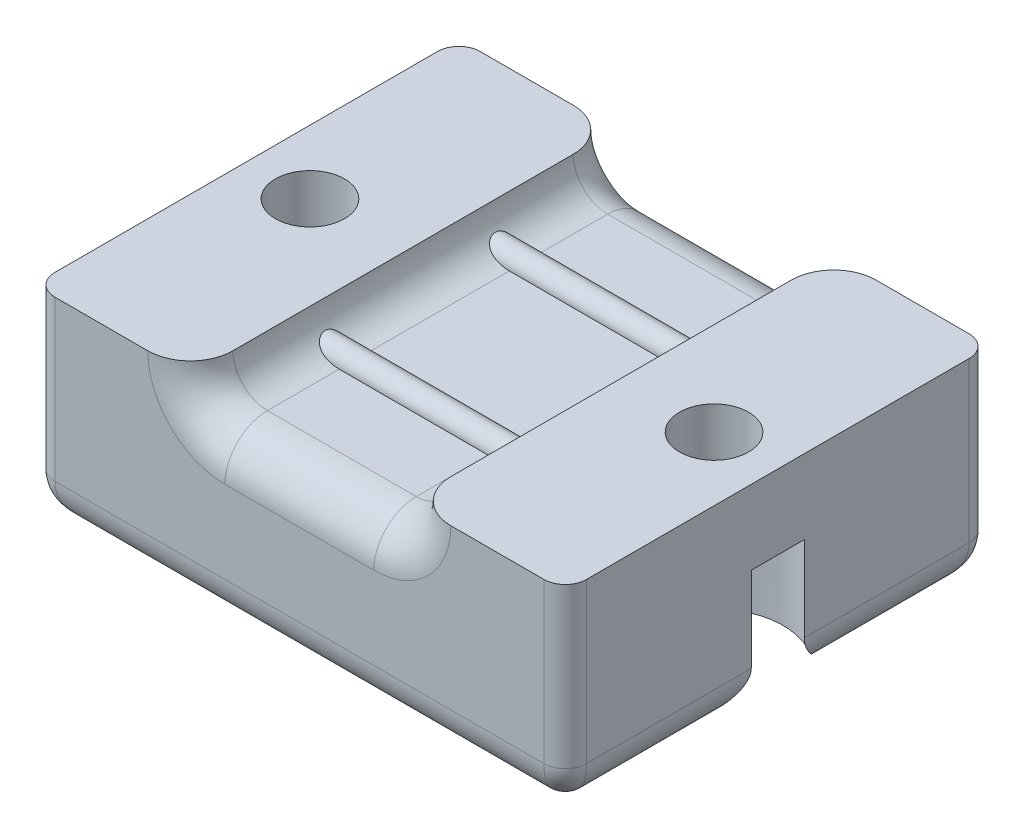
SolidWorks part; units mm, degrees
ref_plane "Front Plane" through (0, 0, 0) normal (0, 0, 1) x (1, 0, 0)
ref_plane "Top Plane" through (0, 0, 0) normal (0, 1, 0) x (1, 0, 0)
ref_plane "Right Plane" through (0, 0, 0) normal (1, 0, 0) x (0, 0, -1)
sketch "Sketch1" plane through (0, 0, 0) normal (0, 1, 0) x (1, 0, 0)
  line L1 (0, 0) -> (50, 0)
  line L2 (0, 0) -> (0, 20)
  line L3 (0, 20) -> (50, 20)
  line L4 (50, 0) -> (50, 20)
  dimension "D1" = 20
  dimension "D2" = 50
extrude "Boss-Extrude1" add sketch "Sketch1" along normal blind 3.5
sketch "Sketch2" plane through (0, 3.5, 0) normal (0, 1, 0) x (1, 0, 0)
  line L0 (50, 20) -> (0, 20) construction
  line L1 (12.5, 20) -> (37.5, 20)
  line L2 (12.5, 20) -> (12.5, 0)
  line L3 (12.5, 0) -> (37.5, 0)
  line L4 (37.5, 20) -> (37.5, 0)
  line L5 (0, 0) -> (50, 0) construction
  point P8 (25, 0)
  point P9 (25, 0)
  dimension "D1" = 25
extrude "Boss-Extrude2" add sketch "Sketch2" along normal blind 6
sketch "Sketch3" plane through (0, 3.5, 0) normal (0, 1, 0) x (1, 0, 0)
  line L0 (50, 0) -> (50, 20) construction
  line L1 (50, 20) -> (37.5, 20) construction
  line L2 (12.5, 20) -> (0, 20) construction
  circle A0 centre (6.25, 10) radius 2.625
  circle A1 centre (43.75, 10) radius 2.625
  point P6 (50, 10)
  point P9 (43.75, 20)
  point P13 (6.25, 20)
  dimension "D1" = 5.25
extrude "Cut-Extrude1" cut sketch "Sketch3" against normal blind 6
sketch "Sketch4" plane through (0, 0, 0) normal (0, 0, 1) x (1, 0, 0)
  line L1 (21.5, 9.5) -> (28.5, 9.5) construction
  line L2 (21.5, 11.125) -> (28.5, 11.125)
  line L3 (21.5, 7.875) -> (28.5, 7.875)
  line L4 (12.5, 9.5) -> (37.5, 9.5) construction
  arc A1 (21.5, 11.125) -> (21.5, 7.875) centre (21.5, 9.5) ccw
  arc A2 (28.5, 7.875) -> (28.5, 11.125) centre (28.5, 9.5) ccw
  point P2 (25, 9.5)
  point P9 (25, 9.5)
  dimension "D1" = 7
  dimension "D2" = 3.25
extrude "Cut-Extrude2" cut sketch "Sketch4" against normal blind 50
sketch "Sketch5" plane through (0, 9.5, 0) normal (0, 1, 0) x (1, 0, 0)
  line L0 (50, 0) -> (50, 20) construction
  line L1 (15.5, 10) -> (34.5, 10) construction
  line L2 (21.5, 20) -> (28.5, 20) construction
  line L3 (12.5, 20) -> (12.5, 0) construction
  circle A0 centre (15.5, 10) radius 1.625
  circle A1 centre (34.5, 10) radius 1.625
  point P4 (25, 10)
  point P7 (50, 10)
  point P10 (25, 20)
  dimension "D2" = 3.25
  dimension "D1" = 3
extrude "Cut-Extrude3" cut sketch "Sketch5" against normal through all
fillet "Fillet1" radius 10 4 edges at (0, 1.75, -20) (0, 1.75, 0) (50, 1.75, -20) (50, 1.75, 0)
fillet "Fillet2" radius 2 2 edges at (37.5, 3.5, -10) (12.5, 3.5, -10)
sketch "Sketch6" plane through (37.5, 0, 0) normal (1, 0, 0) x (0, 0, -1)
  line L0 (6, 7.875) -> (14, 7.875) construction
  line L1 (0, 9.5) -> (20, 9.5) construction
  line L2 (20, 7.875) -> (0, 7.875) construction
  circle A0 centre (6, 7.875) radius 0.625
  circle A1 centre (14, 7.875) radius 0.625
  point P6 (10, 9.5)
  point P7 (10, 7.875)
  dimension "D1" = 1.25
  dimension "D2" = 8
extrude "Boss-Extrude3" add sketch "Sketch6" against normal up to surface (25 mm away) up to face at (12.5, 7.5, -10)
fillet "Fillet3" radius 2 6 edges at (20.351, 8.351, -20) (29.649, 8.351, -20) (20.351, 8.351, 0) (29.649, 8.351, 0) (25, 7.875, -20) (25, 7.875, 0)
sketch "Sketch7" plane through (0, 3.5, 0) normal (0, 1, 0) x (1, 0, 0)
  line L1 (-1.5, 20) -> (12.5, 20)
  line L2 (-1.5, 20) -> (-1.5, 0)
  line L3 (-1.5, 0) -> (12.5, 0)
  line L4 (12.5, 20) -> (12.5, 0)
  line L5 (51.5, 0) -> (37.5, 0)
  line L6 (51.5, 0) -> (51.5, 20)
  line L7 (51.5, 20) -> (37.5, 20)
  line L8 (37.5, 0) -> (37.5, 20)
  line L9 (12.5, 20) -> (12.5, 0) construction
  line L10 (37.5, 0) -> (37.5, 20) construction
  line L11 (17.875, 20) -> (12.5, 20) construction
  point P12 (12.5, 10)
  point P13 (12.5, 10)
  point P14 (37.5, 10)
  point P15 (37.5, 10)
  dimension "D1" = 14
extrude "Cut-Extrude4" cut sketch "Sketch7" against normal blind 7 and the other way blind 7
fillet "Fillet5" radius 1 4 edges at (12.5, 4.75, 0) (37.5, 4.75, 0) (37.5, 4.75, -20) (12.5, 4.75, -20)
fillet "Fillet6" radius 2 8 edges at (37.2071, 0, -19.7071) (37.5, 0, -10) (37.2071, 0, -0.2929) (25, 0, 0) (12.7929, 0, -0.2929) (12.5, 0, -10) (12.7929, 0, -19.7071) (25, 0, -20)
sketch "Sketch8" plane through (0, 0, 0) normal (0, -1, 0) x (1, 0, 0)
  circle A0 centre (34.5, -10) radius 3.25
  circle A1 centre (15.5, -10) radius 3.25
  dimension "D1" = 6.5
extrude "Cut-Extrude6" cut sketch "Sketch8" against normal blind 6
